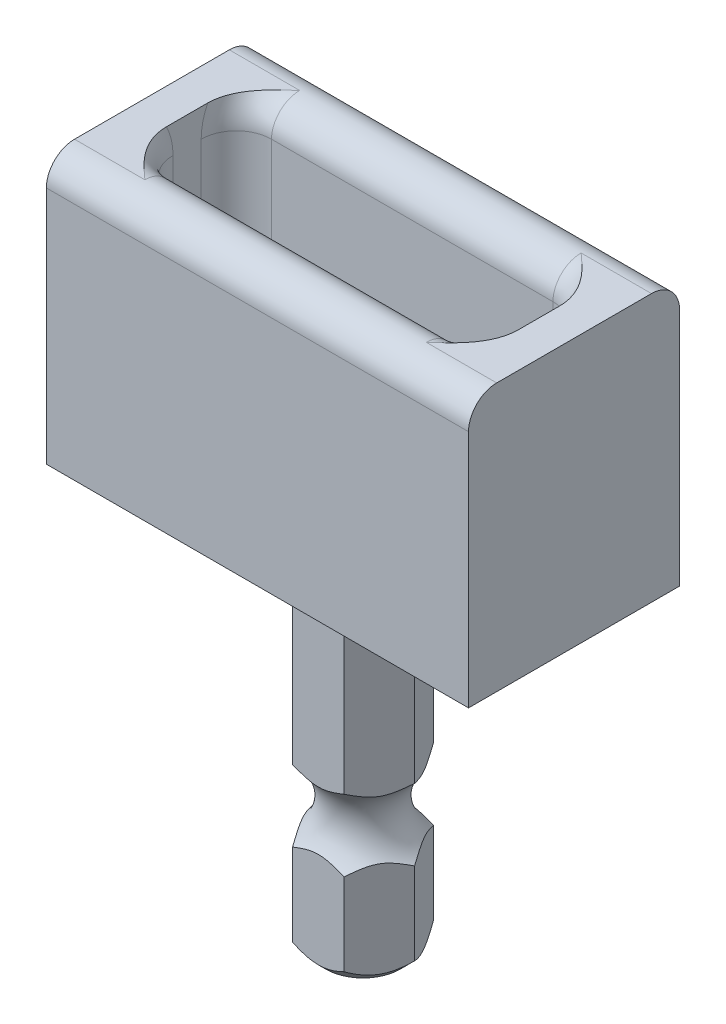
SolidWorks part; units mm, degrees
ref_plane "Front Plane" through (0, 0, 0) normal (0, 0, 1) x (1, 0, 0)
ref_plane "Top Plane" through (0, 0, 0) normal (0, 1, 0) x (1, 0, 0)
ref_plane "Right Plane" through (0, 0, 0) normal (1, 0, 0) x (0, 0, -1)
sketch "Sketch1" plane through (0, 0, 0) normal (0, 1, 0) x (1, 0, 0)
  line L1 (-1.8331, 3.175) -> (-3.6662, 0)
  line L2 (-3.6662, 0) -> (-1.8331, -3.175)
  line L3 (-1.8331, -3.175) -> (1.8331, -3.175)
  line L4 (1.8331, -3.175) -> (3.6662, 0)
  line L5 (3.6662, 0) -> (1.8331, 3.175)
  line L6 (1.8331, 3.175) -> (-1.8331, 3.175)
  circle A0 centre (0, 0) radius 3.175 construction
  dimension "D1" = 6.35
extrude "Boss-Extrude1" add sketch "Sketch1" against normal blind 25
sketch "Sketch2" plane through (0, 0, 0) normal (0, 1, 0) x (1, 0, 0)
  line L1 (-15, 7.5) -> (15, 7.5)
  line L2 (-15, 7.5) -> (-15, -7.5)
  line L3 (-15, -7.5) -> (15, -7.5)
  line L4 (15, 7.5) -> (15, -7.5)
  line L5 (-15, 7.5) -> (15, -7.5) construction
  line L6 (-15, -7.5) -> (15, 7.5) construction
  point P4 (0, 0)
  point P5 (0, 0)
  dimension "D1" = 30
  dimension "D2" = 15
extrude "Boss-Extrude2" add sketch "Sketch2" along normal blind 20
sketch "Sketch3" plane through (0, 0, 0) normal (1, 0, 0) x (0, 0, -1)
  line L0 (-7.5, 20) -> (7.5, 20) construction
  line L1 (-3.5, 20) -> (3.5, 20)
  line L2 (-3.5, 20) -> (-3.5, 5)
  line L3 (-3.5, 5) -> (3.5, 5)
  line L4 (3.5, 20) -> (3.5, 5)
  line L5 (-3.5, 20) -> (3.5, 5) construction
  line L6 (-3.5, 5) -> (3.5, 20) construction
  line L7 (0, 12.5) -> (0, 0) construction
  point P4 (0, 12.5)
  dimension "D1" = 7
  dimension "D2" = 15
extrude "Cut-Extrude1" cut sketch "Sketch3" against normal mid plane 25
fillet "Fillet1" radius 3.5 4 edges at (0, 5, 3.5) (-12.5, 5, 0) (0, 5, -3.5) (12.5, 5, 0)
fillet "Fillet2" radius 2 2 edges at (0, 20, 7.5) (0, 20, 3.5)
fillet "Fillet3" radius 2 2 edges at (0, 20, -7.5) (0, 20, -3.5)
fillet "Fillet5" radius 2.5 10 edges at (-12.5, 13.25, -3.5) (-12.5, 5, 0) (-12.5, 13.25, 3.5) (12.5, 13.25, 3.5) (12.5, 5, 0) (12.5, 13.25, -3.5) (12.5, 19.4142, 4.0858) (12.5, 19.4142, -4.0858) (-12.5, 19.4142, 4.0858) (-12.5, 19.4142, -4.0858)
fillet "Fillet6" [suppressed] radius 1
fillet "Fillet7" radius 2.5 6 edges at (2.7496, 0, 1.5875) (0, 0, 3.175) (-2.7496, 0, 1.5875) (-2.7496, 0, -1.5875) (0, 0, -3.175) (2.7496, 0, -1.5875)
sketch "Sketch4" plane through (0, 0, 0) normal (0, 0, 1) x (1, 0, 0)
  line L0 (-1.8331, -25) -> (1.8331, -25) construction
  line L1 (-3.6662, -13.062) -> (-3.6662, -18.142)
  line L2 (-3.6662, -25) -> (-3.6662, -2.5) construction
  line L3 (0, -25) -> (0, 0) construction
  line L4 (-15, 0) -> (15, 0) construction
  line L5 (-2.413, -15.602) -> (0, -15.602) construction
  line L6 (-2.6502, -25) -> (-4.3832, -25)
  line L7 (-3.6662, -25) -> (-1.8331, -25) construction
  line L8 (-4.3832, -25) -> (-4.3832, -23.267)
  line L9 (-4.3832, -23.267) -> (-2.6502, -25)
  circle A0 centre (-5.6137, -15.602) radius 3.2007
  dimension "D1" = 4.826
  dimension "D2" = 9.398
  dimension "D3" = 5.08
  dimension "D4" = 45
  dimension "D5" = 1.016
revolve "Cut-Revolve1" cut sketch "Sketch4" angle 360 about L3
chamfer "Chamfer1" distance 1 angle 45 4 edges at (0, 0, 7.5) (15, 0, 0) (0, 0, -7.5) (-15, 0, 0)
